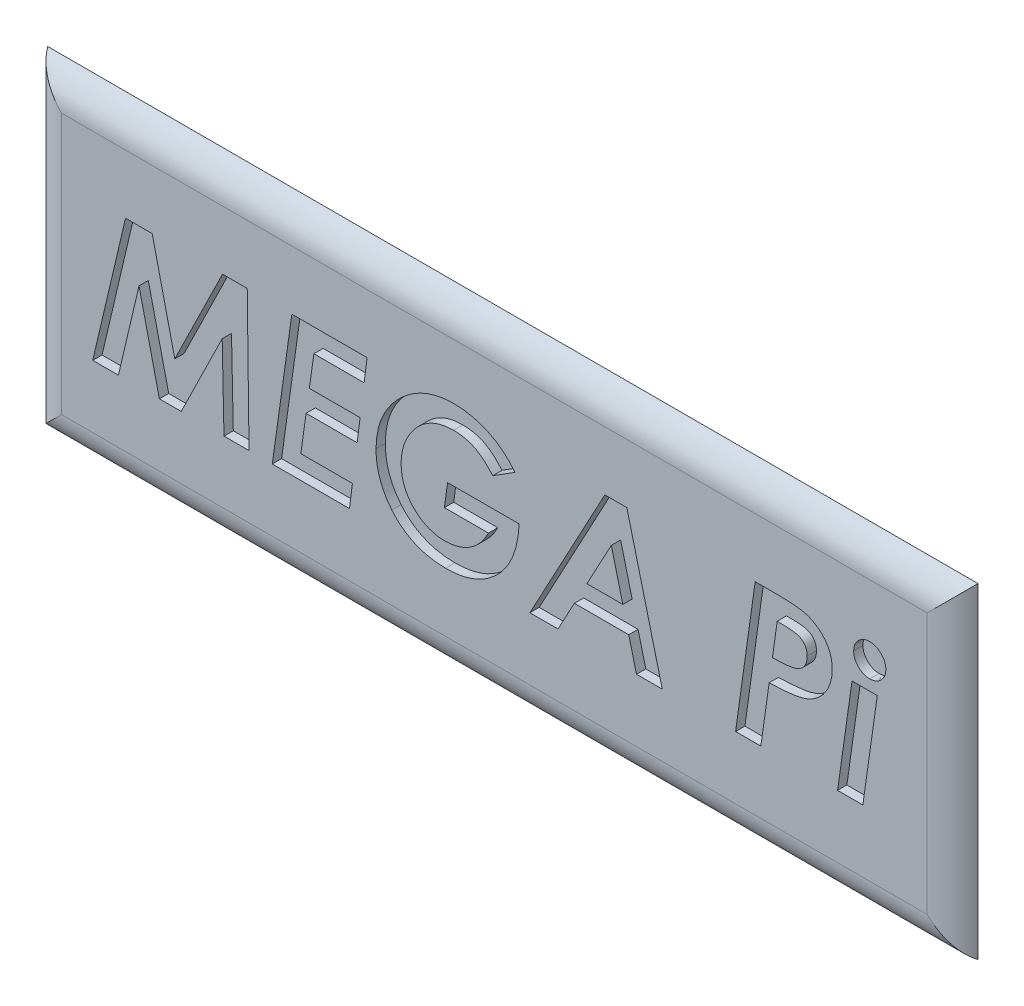
SolidWorks part; units mm, degrees
ref_plane "Plan de face" through (0, 0, 0) normal (0, 0, 1) x (1, 0, 0)
ref_plane "Plan de dessus" through (0, 0, 0) normal (0, 1, 0) x (1, 0, 0)
ref_plane "Plan de droite" through (0, 0, 0) normal (1, 0, 0) x (0, 0, -1)
sketch "Sketch1" plane through (0, 0, 0) normal (0, 0, 1) x (1, 0, 0)
  line L1 (0, 0) -> (100, 0)
  line L2 (0, 0) -> (0, 35)
  line L3 (0, 35) -> (100, 35)
  line L4 (100, 0) -> (100, 35)
  dimension "D1" = 100
  dimension "D2" = 35
extrude "Boss-Extrude1" add sketch "Sketch1" along normal blind 2
sketch "Sketch2" plane through (0, 0, 2) normal (0, 0, 1) x (1, 0, 0)
  text T0 "<b><i>MEGA Pi</i></b>" font "Century Gothic" height 15
extrude "Cut-Extrude1" cut sketch "Sketch2" against normal blind 1
fillet "Fillet1" radius 4 4 edges at (100, 17.5, 2) (50, 0, 2) (0, 17.5, 2) (50, 35, 2)
